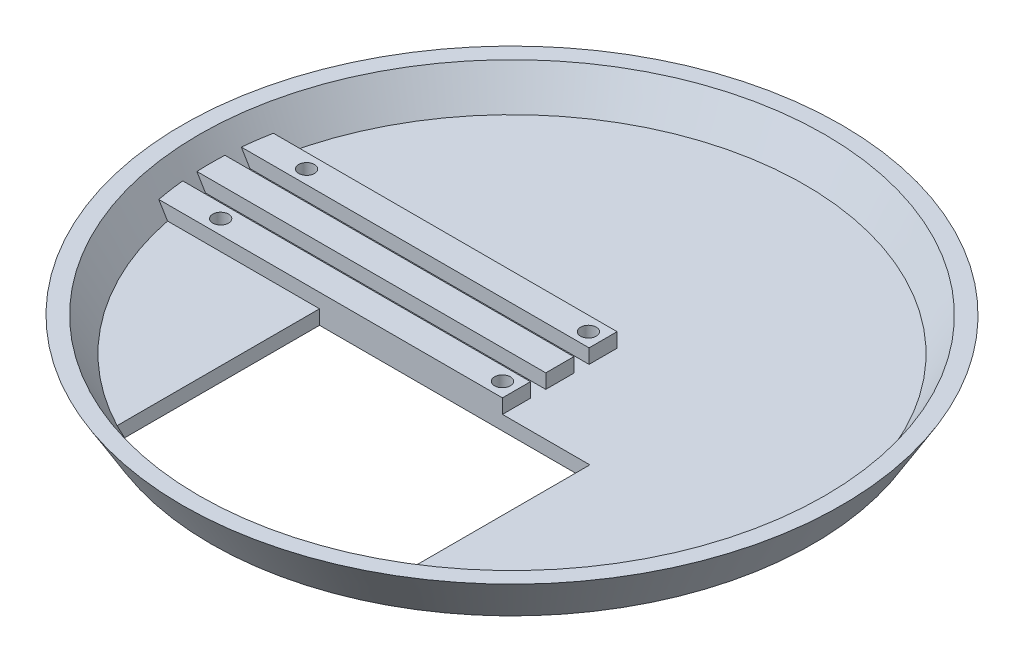
SolidWorks part; units mm, degrees
ref_plane "Front Plane" through (0, 0, 0) normal (0, 0, 1) x (1, 0, 0)
ref_plane "Top Plane" through (0, 0, 0) normal (0, 1, 0) x (1, 0, 0)
ref_plane "Right Plane" through (0, 0, 0) normal (1, 0, 0) x (0, 0, -1)
sketch "Sketch1" plane through (0, 0, 0) normal (0, 0, 1) x (1, 0, 0)
  line L0 (0, 0) -> (63, 0)
  line L1 (63, 0) -> (69, 10)
  line L6 (0, 3) -> (61.3014, 3)
  line L7 (61.3014, 3) -> (65.5014, 10)
  line L8 (69, 10) -> (65.5014, 10)
  line L9 (0, 0) -> (0, 3)
  line L10 (61.3014, 3) -> (66.4275, 11.5435) construction
  dimension "D1" = 69
  dimension "D2" = 63
  dimension "D3" = 10
  dimension "D4" = 3
revolve "Revolve1" add sketch "Sketch1" angle 360 about L9
sketch "Sketch2" plane through (0, 3, 0) normal (0, 1, 0) x (1, 0, 0)
  line L0 (-28.3, -12) -> (-28.3, -54.3781)
  line L1 (-28.3, -12) -> (28.3, -12)
  line L5 (28.3, -12) -> (28.3, -54.3781)
  arc A0 (-28.3, -54.3781) -> (28.3, -54.3781) centre (0, 0) ccw
  circle A3 centre (0, 0) radius 61.3014 construction
  dimension "D2" = 28.3
  dimension "D1" = 56.6
  dimension "D4" = 12
extrude "Cut-Extrude1" cut sketch "Sketch2" against normal through all
sketch "Sketch4" plane through (0, 0, 0) normal (1, 0, 0) x (0, 0, -1)
  line L0 (-6.1333, 3) -> (-12, 3)
  line L5 (-12, 3) -> (-12, 6)
  line L6 (-12, 6) -> (-6.1333, 6)
  line L7 (-6.1333, 6) -> (-6.1333, 3)
  line L8 (-2.9333, 3) -> (2.9333, 3)
  line L9 (2.9333, 3) -> (2.9333, 6)
  line L10 (2.9333, 6) -> (-2.9333, 6)
  line L11 (-2.9333, 6) -> (-2.9333, 3)
  line L12 (12, 3) -> (6.1333, 3)
  line L13 (6.1333, 3) -> (6.1333, 6)
  line L14 (6.1333, 6) -> (12, 6)
  line L15 (12, 6) -> (12, 3)
  point P6 (-2.9333, 6)
  point P13 (0, 3)
  dimension "D1" = 12
  dimension "D2" = 3
  dimension "D3" = 3
  dimension "D4" = 3.2
  dimension "D5" = 3.2
  dimension "D6" = 12
extrude "Boss-Extrude1" add sketch "Sketch4" along normal blind 10 and the other way blind 63.5
sketch "Sketch5" plane through (0, 0, 0) normal (0, 1, 0) x (1, 0, 0)
  line L0 (10, 2.9333) -> (10, -2.9333) construction
  circle A0 centre (7, -9) radius 1.65
  circle A1 centre (7, -9.7468) radius 1.65
  circle A2 centre (7, 9) radius 1.65
  circle A6 centre (-52, 9) radius 1.65
  circle A8 centre (-52, -9) radius 1.65
  circle A9 centre (-22.5, -9.7468) radius 1.65 [skipped]
  circle A10 centre (-52, -9.7468) radius 1.65 [skipped]
  circle A11 centre (-22.5, 9) radius 1.65 [skipped]
  circle A12 centre (-22.5, -9) radius 1.65 [skipped]
  dimension "D1" = 12
  dimension "D2" = 3.3
  dimension "D3" = 9
  dimension "D6" = 3
  dimension "D7" = 59
  dimension "D4" = 9
  dimension "D5" = 3
extrude "Cut-Extrude2" cut sketch "Sketch5" along normal through all contours A2 | A0 | A8 | A6
